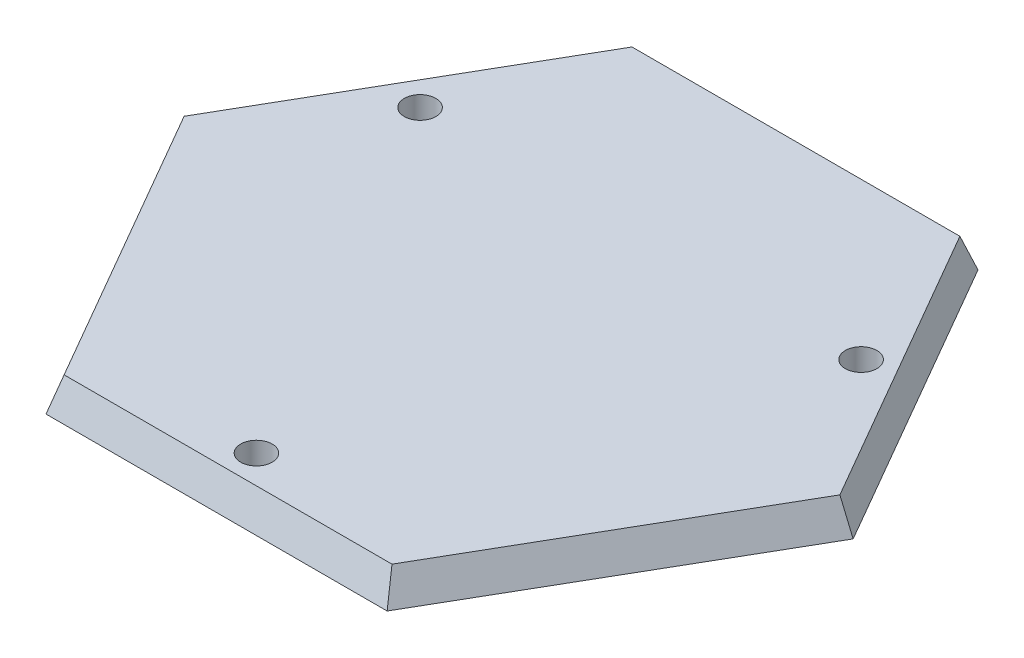
SolidWorks part; units mm, degrees
ref_plane "Front Plane" through (0, 0, 0) normal (0, 0, 1) x (1, 0, 0)
ref_plane "Top Plane" through (0, 0, 0) normal (0, 1, 0) x (1, 0, 0)
ref_plane "Right Plane" through (0, 0, 0) normal (1, 0, 0) x (0, 0, -1)
sketch "Sketch1" plane through (0, 0, 0) normal (0, 1, 0) x (1, 0, 0)
  line L0 (0, 0) -> (-77.9423, 45) construction
  line L1 (103.923, 0) -> (51.9615, 90)
  line L2 (51.9615, 90) -> (-51.9615, 90)
  line L3 (-51.9615, 90) -> (-103.923, 0)
  line L4 (-103.923, 0) -> (-51.9615, -90)
  line L5 (-51.9615, -90) -> (51.9615, -90)
  line L6 (51.9615, -90) -> (103.923, 0)
  line L7 (0, 0) -> (77.9423, 45) construction
  line L8 (0, 0) -> (0, -90) construction
  circle A0 centre (0, 0) radius 90 construction
  circle A1 centre (0, -81) radius 5
  circle A2 centre (70.1481, 40.5) radius 5
  circle A3 centre (-68.9423, 39.8038) radius 5
  dimension "D2" = 10
  dimension "D3" = 10
  dimension "D4" = 10
  dimension "D1" = 90
  dimension "D5" = 9
  dimension "D6" = 9
  dimension "D7" = 9
extrude "Boss-Extrude1" add sketch "Sketch1" against normal blind 10 draft 20 contours L4 L5 L6 L1 L2 L3 draft outward yes
extrude "Cut-Extrude1" cut sketch "Sketch1<4>" against normal up to surface (10 mm away) contours A3 | A2 | A1 up to face at (0, -10, 0)
sketch "Sketch1<4>" plane through (0, 0, 0) normal (0, 1, 0) x (1, 0, 0) same geometry as "Sketch1"
